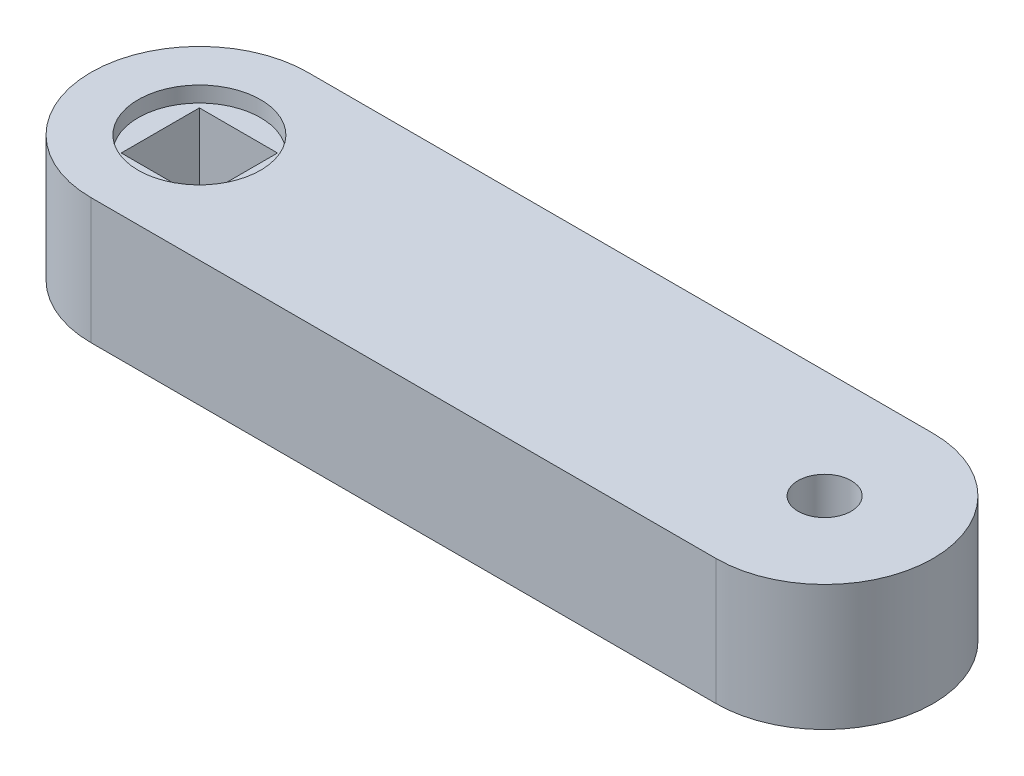
SolidWorks part; units mm, degrees
ref_plane "Front Plane" through (0, 0, 0) normal (0, 0, 1) x (1, 0, 0)
ref_plane "Top Plane" through (0, 0, 0) normal (0, 1, 0) x (1, 0, 0)
ref_plane "Right Plane" through (0, 0, 0) normal (1, 0, 0) x (0, 0, -1)
sketch "Sketch1" plane through (0, 0, 0) normal (0, 1, 0) x (1, 0, 0)
  line L0 (0, 0) -> (50.8, 0) construction
  line L1 (0, 8.8113) -> (50.8, 8.8113)
  line L2 (0, -8.8113) -> (50.8, -8.8113)
  arc A1 (0, 8.8113) -> (0, -8.8113) centre (0, 0) ccw
  arc A2 (50.8, -8.8113) -> (50.8, 8.8113) centre (50.8, 0) ccw
  point P3 (25.4, 0)
  dimension "D1" = 17.6226
  dimension "D2" = 50.8
extrude "Boss-Extrude1" add sketch "Sketch1" along normal blind 10.2108
sketch "Sketch2" plane through (0, 10.2108, 0) normal (0, 1, 0) x (1, 0, 0)
  line L1 (-3.175, 3.175) -> (3.175, 3.175)
  line L2 (-3.175, 3.175) -> (-3.175, -3.175)
  line L3 (-3.175, -3.175) -> (3.175, -3.175)
  line L4 (3.175, 3.175) -> (3.175, -3.175)
  line L5 (-3.175, 3.175) -> (3.175, -3.175) construction
  line L6 (-3.175, -3.175) -> (3.175, 3.175) construction
  circle A1 centre (50.8, 0) radius 2.159
  point P0 (0, 0)
  point P9 (0, 0)
  dimension "D2" = 6.35
  dimension "D3" = 4.318
  dimension "D1" = 6.35
  dimension "D4" = 50.8
extrude "Cut-Extrude1" cut sketch "Sketch2" against normal through all
sketch "Sketch3" plane through (0, 10.2108, 0) normal (0, 1, 0) x (1, 0, 0)
  circle A0 centre (0, 0) radius 4.9721
  dimension "D1" = 9.9441
extrude "Cut-Extrude2" cut sketch "Sketch3" against normal blind 1.27
ref_plane "Plane1" through (0, 5.1054, 0) normal (0, 1, 0) x (1, 0, 0)
mirror "Mirror1" about plane through (0, 5.1054, 0) normal (0, 1, 0) of "Cut-Extrude2"
